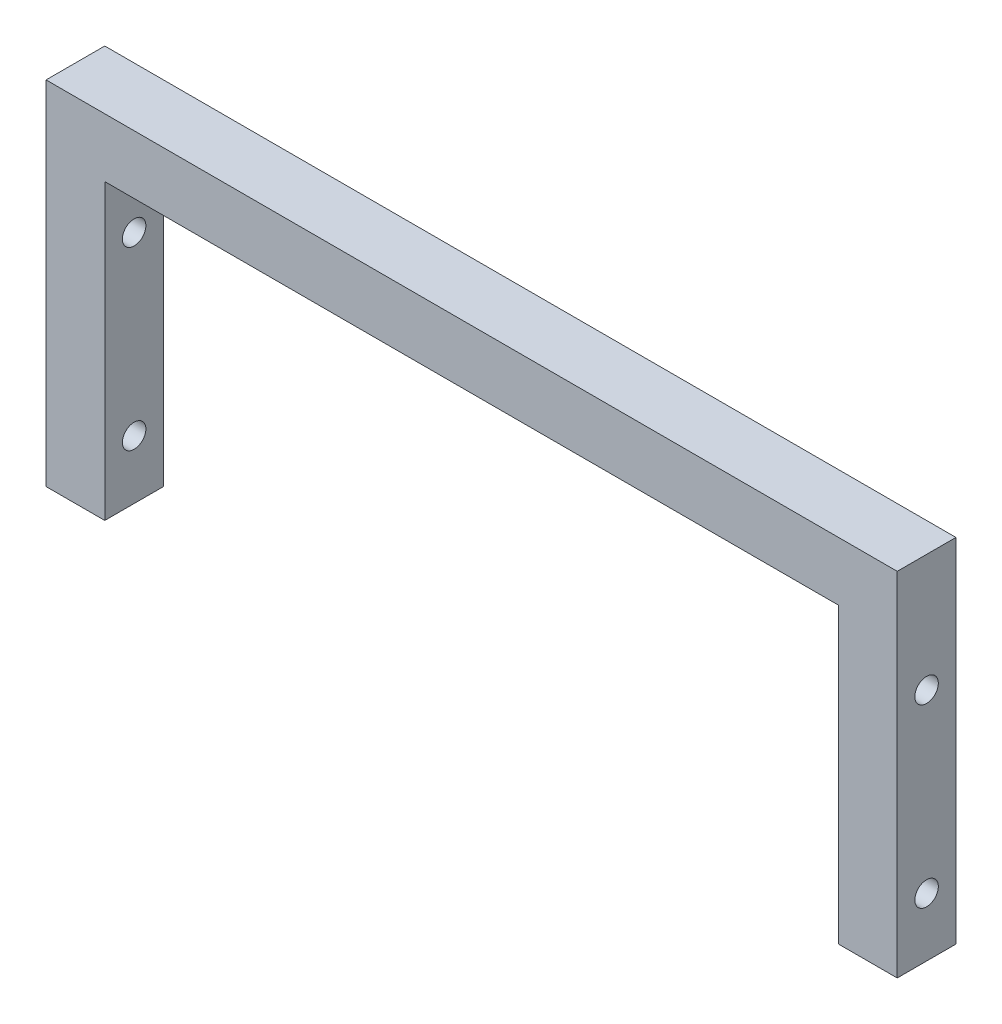
SolidWorks part; units mm, degrees
material "2014-O"
ref_plane "Front" through (0, 0, 0) normal (0, 0, 1) x (1, 0, 0)
ref_plane "Top" through (0, 0, 0) normal (0, 1, 0) x (1, 0, 0)
ref_plane "Right" through (0, 0, 0) normal (1, 0, 0) x (0, 0, -1)
sketch "Sketch1" plane through (0, 0, 0) normal (0, 0, 1) x (1, 0, 0)
  line L0 (0, 0) -> (0, 60)
  line L1 (0, 60) -> (145, 60)
  line L2 (145, 60) -> (145, 0)
  line L3 (145, 0) -> (135, 0)
  line L4 (135, 0) -> (135, 50)
  line L5 (135, 50) -> (10, 50)
  line L6 (10, 50) -> (10, 0)
  line L7 (10, 0) -> (0, 0)
  dimension "D1" = 125
  dimension "D2" = 50
  dimension "D3" = 10
  dimension "D4" = 10
  dimension "D5" = 10
extrude "Boss-Extrude1" add sketch "Sketch1" along normal blind 10
sketch "Sketch4" plane through (145, 0, 0) normal (1, 0, 0) x (0, 0, -1)
  line L0 (-10, 60) -> (0, 60) construction
  line L1 (-10, 0) -> (0, 0) construction
  line L2 (-10, 0) -> (-10, 60) construction
  circle A0 centre (-5, 10) radius 2
  circle A1 centre (-5, 40) radius 2
  dimension "D1" = 4
  dimension "D2" = 20
  dimension "D3" = 10
  dimension "D4" = 5
  dimension "D5" = 5
extrude "Cut-Extrude1" cut sketch "Sketch4" against normal through all both and the other way through all
sketch "Sketch3" plane through (0, 0, 10) normal (0, 0, 1) x (1, 0, 0)
  line L5 (145, 60) -> (0, 60) construction
  line L6 (87.5, 60) -> (57.5, 60)
  line L7 (87.5, 60) -> (87.5, 80)
  line L8 (87.5, 80) -> (57.5, 80)
  line L9 (57.5, 60) -> (57.5, 80)
  line L10 (145, 60) -> (87.5, 60) construction
  line L11 (82.5, 75) -> (62.5, 75)
  line L12 (82.5, 75) -> (82.5, 65)
  line L13 (82.5, 65) -> (62.5, 65)
  line L14 (62.5, 75) -> (62.5, 65)
  line L15 (57.5, 60) -> (0, 60) construction
  dimension "D1" = 5
  dimension "D2" = 5
  dimension "D3" = 5
  dimension "D4" = 5
  dimension "D5" = 20
  dimension "D6" = 30
extrude "Boss-Extrude2" [suppressed] add sketch "Sketch3" against normal up to surface (10 mm away)
ref_plane "Plane1" through (0, 0, 5) normal (0, 0, 1) x (1, 0, 0)
ref_plane "Plane2" through (72.5, 0, 0) normal (-1, 0, 0) x (0, 0, 1)
ref_axis "Axis2" through (145, 60, 10) along (-1, 0, 0)
